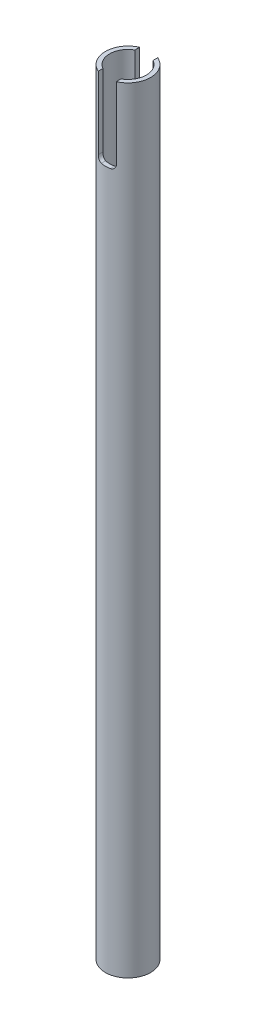
SolidWorks part; units mm, degrees
note: The reader was unsure of these and kept them because the rebuilt part matched: shared geometry of "Sketch1<3>".
material "AISI 4130 Steel, annealed at 865C"
ref_plane "X-Y Datum" through (0, 0, 0) normal (0, 0, 1) x (1, 0, 0)
ref_plane "X-Z Datum" through (0, 0, 0) normal (0, 1, 0) x (1, 0, 0)
ref_plane "Y-Z Datum" through (0, 0, 0) normal (1, 0, 0) x (0, 0, -1)
sketch "Sketch1" plane through (0, 0, 0) normal (0, 1, 0) x (1, 0, 0)
  circle A0 centre (0, 0) radius 7.9375
  circle A1 centre (0, 0) radius 6.4643
  dimension "D1" = 15.875
  dimension "D2" = 12.9286
extrude "Boss-Extrude1" add sketch "Sketch1" along normal blind 25.4
ref_plane "Plane1" through (7.9375, 0, 0) normal (1, 0, 0) x (0, 0, -1)
sketch "Sketch2" plane through (7.9375, 0, 0) normal (1, 0, 0) x (0, 0, -1)
  line L0 (-3.175, 0) -> (-3.175, 26.9875)
  line L1 (-7.9375, 0) -> (7.9375, 0) construction
  line L2 (-3.175, 26.9875) -> (3.175, 26.9875)
  line L3 (3.175, 26.9875) -> (3.175, 0)
  line L4 (7.9375, 0) -> (7.9375, 25.4) construction
  line L5 (-3.175, 0) -> (3.175, 0)
  dimension "D1" = 6.35
  dimension "D2" = 26.9875
  dimension "D3" = 4.7625
ref_plane "Plane2" through (0, 0, -7.9375) normal (0, 0, -1) x (-1, 0, 0)
extrude "Boss-Extrude2" add sketch "Sketch1<3>" along normal offset from surface 25.4 and the other way up to surface
sketch "Sketch1<3>" plane through (0, 0, 0) normal (0, 1, 0) x (1, 0, 0) same geometry as "Sketch1"
sketch "Sketch4" plane through (282.8448, -431.6209, -7.9375) normal (0, 0, 1) x (0.8492, 0.528, 0)
  line L0 (65.1945, 634.4863) -> (51.7823, 612.9162)
  line L1 (69.2389, 631.9715) -> (55.7575, 640.3542) construction
  line L4 (67.9878, 632.7494) -> (57.0086, 639.5763) construction
  line L5 (59.802, 637.8394) -> (65.1945, 634.4863)
  line L6 (49.5959, 612.4063) -> (46.8996, 614.0828)
  line L7 (60.3653, 626.7198) -> (74.2345, 649.0249) construction
  line L10 (46.3897, 616.2692) -> (59.802, 637.8394)
  arc A0 (51.7823, 612.9162) -> (49.5959, 612.4063) centre (50.4341, 613.7544) cw
  arc A1 (46.8996, 614.0828) -> (46.3897, 616.2692) centre (47.7379, 615.4309) cw
  point P14 (45.5515, 614.9211)
  dimension "D3" = 1.5875
  dimension "D1" = 6.35
  dimension "D2" = 26.9875
extrude "Cut-Extrude1" cut sketch "Sketch4" along normal through all
